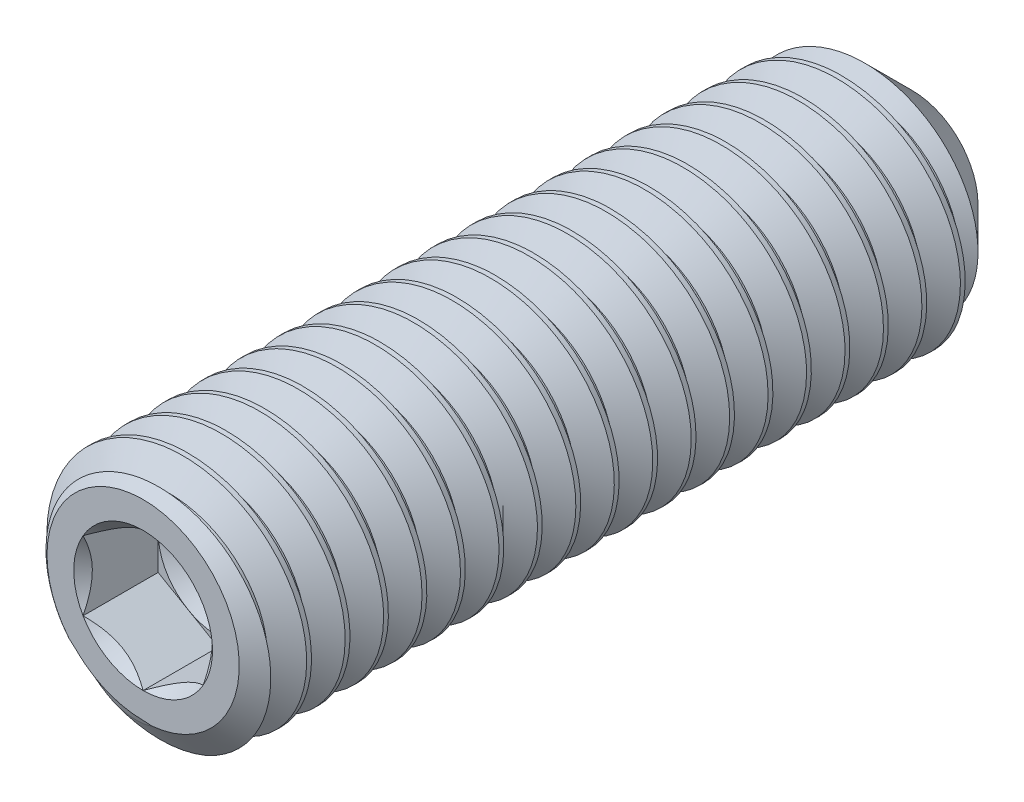
SolidWorks part; units mm, degrees
ref_plane "Front" through (0, 0, 0) normal (0, 0, 1) x (1, 0, 0)
ref_plane "Top" through (0, 0, 0) normal (0, 1, 0) x (1, 0, 0)
ref_plane "Right" through (0, 0, 0) normal (1, 0, 0) x (0, 0, -1)
sketch "Sketch22" plane through (0, 0, 0) normal (1, 0, 0) x (0, 0, -1)
  line L0 (-7.5884, 0) -> (-7.5884, 2)
  line L1 (-7.5884, 2) -> (-7.2383, 2.5)
  line L2 (-7.2383, 2.5) -> (7.2815, 2.5)
  line L3 (7.2815, 2.5) -> (8.4116, 1.3699)
  line L4 (8.4116, 1.3699) -> (7.5884, 0)
  line L5 (7.5884, 0) -> (-7.5884, 0)
  line L6 (7.5884, 0) -> (8.4116, 0) construction
  line L7 (8.4116, 0) -> (8.4116, 1.3699) construction
  line L8 (8.4116, -1.3699) -> (7.5884, 0) construction
  line L9 (-7.2383, -2.5) -> (7.2815, -2.5) construction
  dimension "Dia" = 5
  dimension "Length" = 16
  dimension "D3" = 35
  dimension "D5" = 118
  dimension "D6" = 45
  dimension "D7" = 4
revolve "Revolve1" add sketch "Sketch22" angle 360 about L6
ref_plane "Plane1" through (0, 0, -8.4116) normal (0, 0, 1) x (1, 0, 0)
sketch "Sketch27" plane through (0, 0, -8.4116) normal (0, 0, 1) x (1, 0, 0)
  circle A0 centre (0, 0) radius 2.5 construction
  circle A1 centre (0, 0) radius 2.5
curve "Helix/Spiral1" pitch 0.8 height 16.8 turns 21
sketch "Sketch28" plane through (0, 0, 0) normal (1, 0, 0) x (0, 0, -1)
  line L0 (8.4116, 2.5) -> (9.1116, 2.5)
  line L1 (9.1116, 2.5) -> (8.8116, 1.9804)
  line L2 (8.8116, 1.9804) -> (8.7116, 1.9804)
  line L3 (8.7116, 1.9804) -> (8.4116, 2.5)
  line L4 (8.5616, 2.2402) -> (8.9616, 2.2402) construction
  line L6 (-7.2383, 2.5) -> (7.2815, 2.5) construction
  dimension "D1" = 0.1
  dimension "D3" = 60
  dimension "D2" = 0.4
sweep "Cut-Sweep2" cut profiles "Sketch28" path "Helix/Spiral1" align with end faces yes
sketch "Sketch23" plane through (0, 0, 7.5884) normal (0, 0, 1) x (1, 0, 0)
  line L1 (0, 1.4434) -> (-1.25, 0.7217)
  line L2 (-1.25, 0.7217) -> (-1.25, -0.7217)
  line L3 (-1.25, -0.7217) -> (0, -1.4434)
  line L4 (0, -1.4434) -> (1.25, -0.7217)
  line L5 (1.25, -0.7217) -> (1.25, 0.7217)
  line L6 (1.25, 0.7217) -> (0, 1.4434)
  circle A0 centre (0, 0) radius 1.25 construction
  dimension "Hex" = 2.5
extrude "Cut-Extrude10" cut sketch "Sketch23" against normal blind 1.5625
sketch "Sketch24" plane through (0, 0, 7.5884) normal (0, 0, 1) x (1, 0, 0)
  circle A0 centre (0, 0) radius 1.4434
extrude "Cut-Extrude11" cut sketch "Sketch24" against normal through all draft 45
sketch "Sketch26" plane through (0, 0, 6.0259) normal (0, 0, 1) x (1, 0, 0)
  circle A0 centre (0, 0) radius 1.25 construction
  circle A1 centre (0, 0) radius 1.25
extrude "Cut-Extrude12" cut sketch "Sketch26" against normal through all draft 60
sketch "Sketch30" plane through (0, 0, 0) normal (1, 0, 0) x (0, 0, -1)
  line L0 (-7.2383, 2.5) -> (7.2815, 2.5) construction
  line L1 (-7.5884, 0) -> (-7.5884, 2) construction
  line L2 (8.4116, 0) -> (8.4116, 1.3699) construction
  line L3 (-7.2383, -2.5) -> (7.2815, -2.5) construction
  point P0 (-7.5884, 2.5)
  point P1 (8.4116, 2.5)
  point P2 (8.4116, -2.5)
  point P11 (7.2116, -2.5)
  dimension "D1" = 1.2
sketch "Sketch31" plane through (0, 0, 0) normal (1, 0, 0) x (0, 0, -1)
  line L2 (7.5884, 0) -> (8.4116, -1.3699)
  line L3 (8.4116, 1.3699) -> (7.5884, 0)
equation "\"D7@Sketch22\"=\"Dia@Sketch22\"*.8"
equation "\"D1@Sketch28\" = \"D4@Helix/Spiral1\" * .125"
equation "\"D2@Sketch28\" = \"D4@Helix/Spiral1\" * .5"
equation "\"D3@Helix/Spiral1\" = \"Length@Sketch22\" + \"D4@Helix/Spiral1\""
equation "\"D1@Sketch30\" = \"D4@Helix/Spiral1\" * 1.5"
equation "\"hex Depth@Cut-Extrude10\" = \"Hex@Sketch23\" * .625"
